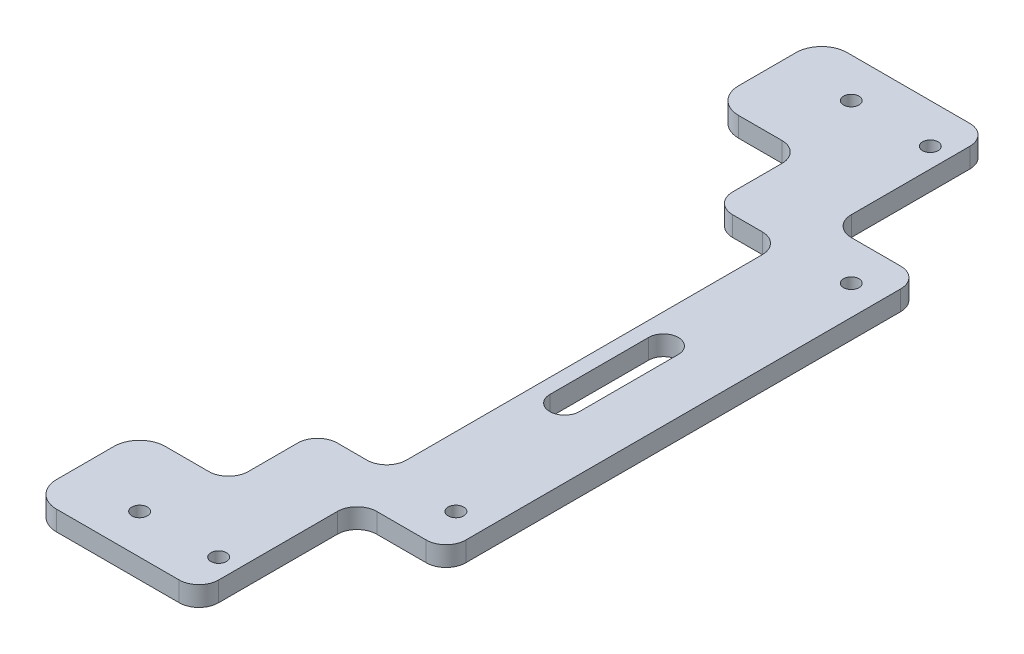
SolidWorks part; units mm, degrees
material "PC High Viscosity"
ref_plane "Front Plane" through (0, 0, 0) normal (0, 0, 1) x (1, 0, 0)
ref_plane "Top Plane" through (0, 0, 0) normal (0, 1, 0) x (1, 0, 0)
ref_plane "Right Plane" through (0, 0, 0) normal (1, 0, 0) x (0, 0, -1)
sketch "Sketch1" plane through (0, 0, 0) normal (0, 1, 0) x (1, 0, 0)
  line L0 (0, 0) -> (0, 50.8)
  line L5 (0, 50.8) -> (-28.575, 50.8)
  line L6 (-28.575, 50.8) -> (-28.575, 203.2)
  line L7 (-28.575, 203.2) -> (0, 203.2)
  line L8 (0, 203.2) -> (0, 254)
  line L9 (0, 254) -> (215.9, 254)
  line L10 (215.9, 254) -> (215.9, 203.2)
  line L11 (215.9, 203.2) -> (244.475, 203.2)
  line L12 (244.475, 203.2) -> (244.475, 50.8)
  line L13 (244.475, 50.8) -> (215.9, 50.8)
  line L14 (215.9, 50.8) -> (215.9, 0)
  line L15 (215.9, 0) -> (0, 0)
  line L16 (101.6, 219.075) -> (101.6, 34.925) construction
  line L17 (12.7, 219.075) -> (190.5, 219.075)
  line L18 (12.7, 219.075) -> (12.7, 34.925)
  line L19 (12.7, 34.925) -> (190.5, 34.925)
  line L20 (190.5, 219.075) -> (190.5, 34.925)
  line L21 (-9.525, 63.5) -> (12.7, 63.5)
  line L22 (-9.525, 63.5) -> (-9.525, 190.5)
  line L23 (-9.525, 190.5) -> (12.7, 190.5)
  line L24 (12.7, 63.5) -> (12.7, 190.5)
  line L25 (212.725, 190.5) -> (190.5, 190.5)
  line L26 (190.5, 63.5) -> (190.5, 190.5)
  line L27 (212.725, 63.5) -> (190.5, 63.5)
  line L28 (212.725, 63.5) -> (212.725, 190.5)
  line L29 (12.7, 127) -> (-9.525, 127) construction
  line L30 (-19.05, 111.125) -> (-19.05, 142.875) construction
  line L31 (-23.8125, 111.125) -> (-23.8125, 142.875)
  line L32 (-14.2875, 111.125) -> (-14.2875, 142.875)
  line L33 (222.25, 111.125) -> (222.25, 142.875) construction
  line L34 (227.0125, 111.125) -> (227.0125, 142.875)
  line L35 (217.4875, 111.125) -> (217.4875, 142.875)
  line L36 (12.7, 219.075) -> (12.7, 254) construction
  line L37 (12.7, 34.925) -> (12.7, 0) construction
  circle A0 centre (209.55, 241.3) radius 2.4892
  circle A1 centre (209.55, 12.7) radius 2.4892
  arc A2 (-23.8125, 111.125) -> (-14.2875, 111.125) centre (-19.05, 111.125) ccw
  arc A3 (-14.2875, 142.875) -> (-23.8125, 142.875) centre (-19.05, 142.875) ccw
  arc A4 (227.0125, 111.125) -> (217.4875, 111.125) centre (222.25, 111.125) cw
  arc A5 (217.4875, 142.875) -> (227.0125, 142.875) centre (222.25, 142.875) cw
  point P34 (-19.05, 127)
  point P44 (222.25, 127)
  dimension "D10" = 4.9784
  dimension "D1" = 177.8
  dimension "D5" = 12.7
  dimension "D6" = 25.4
  dimension "D7" = 152.4
  dimension "D8" = 22.225
  dimension "D9" = 19.05
  dimension "D11" = 12.7
  dimension "D12" = 12.7
  dimension "D13" = 6.35
  dimension "D14" = 12.7
  dimension "D15" = 9.525
  dimension "D16" = 9.525
  dimension "D17" = 31.75
  dimension "D2" = 254
  dimension "D3" = 184.15
extrude "Boss-Extrude1" add sketch "Sketch1" along normal mid plane 6.35 contours L15 L14 L13 L12 L11 L10 L9 L8 L7 L6 L5 L0 A1 A0 L28 L27 L20 L19 L18 L21 L22 L23 L17 L25 region at (3.7292, 0, -25.4)
fillet "Fillet1" radius 6.35 24 edges at (0, 0, 0) (0, 0, -50.8) (-28.575, 0, -50.8) (-28.575, 0, -203.2) (0, 0, -203.2) (0, 0, -254) (215.9, 0, -254) (215.9, 0, -203.2) (244.475, 0, -203.2) (244.475, 0, -50.8) (215.9, 0, -50.8) (215.9, 0, 0) (212.725, 0, -190.5) (190.5, 0, -190.5) (190.5, 0, -219.075) (12.7, 0, -219.075) (-9.525, 0, -190.5) (-9.525, 0, -63.5) (12.7, 0, -63.5) (12.7, 0, -34.925) (190.5, 0, -34.925) (190.5, 0, -63.5) (212.725, 0, -63.5) (12.7, 0, -190.5)
pattern_linear "LPattern1" count 8 spacing 25.4 along (-1, 0, 0) of face at (209.55, 3.175, -238.8108) of face at (209.55, 3.175, -10.2108)
sketch "Sketch2" plane through (0, 3.175, 0) normal (0, 1, 0) x (1, 0, 0)
  line L0 (6.35, 254) -> (209.55, 254) construction
  line L1 (161.925, 254) -> (-28.575, 254)
  line L2 (161.925, 254) -> (161.925, 0)
  line L3 (161.925, 0) -> (-28.575, 0)
  line L4 (-28.575, 254) -> (-28.575, 0)
  line L5 (209.55, 0) -> (6.35, 0) construction
  line L6 (-28.575, 57.15) -> (-28.575, 196.85) construction
  line L7 (234.95, 190.5) -> (234.95, 63.5) construction
  line L8 (244.475, 196.85) -> (244.475, 57.15) construction
  line L9 (217.4875, 111.125) -> (217.4875, 142.875) construction
  line L10 (222.25, 203.2) -> (238.125, 203.2) construction
  circle A1 centre (184.15, 241.3) radius 2.4892 construction
  circle A2 centre (234.95, 190.5) radius 2.4892
  circle A3 centre (234.95, 63.5) radius 2.4892
  point P16 (234.95, 127)
  point P17 (217.4875, 127)
  dimension "D1" = 22.225
  dimension "D2" = 4.9784
  dimension "D3" = 12.7
  dimension "D4" = 9.525
extrude "Cut-Extrude1" cut sketch "Sketch2" against normal through all
fillet "Fillet2" radius 8.255 4 edges at (161.925, 0, -219.075) (161.925, 0, -254) (161.925, 0, 0) (161.925, 0, -34.925)
equation "\"D14@Sketch1\"=\"D5@Sketch1\""
